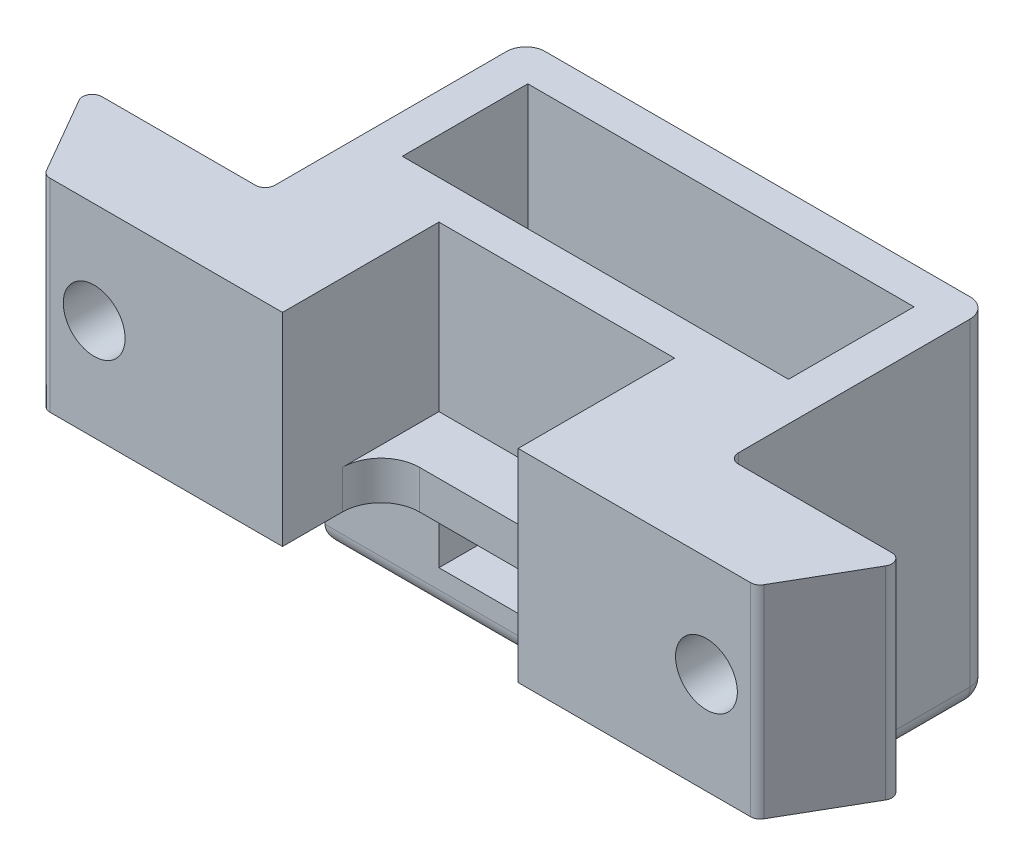
SolidWorks part; units mm, degrees
ref_plane "Front Plane" through (0, 0, 0) normal (0, 0, 1) x (1, 0, 0)
ref_plane "Top Plane" through (0, 0, 0) normal (0, 1, 0) x (1, 0, 0)
ref_plane "Right Plane" through (0, 0, 0) normal (1, 0, 0) x (0, 0, -1)
sketch "Sketch1" plane through (0, 0, 0) normal (0, 1, 0) x (1, 0, 0)
  line L0 (0, 0) -> (0, 8.1)
  line L1 (0, 8.1) -> (12.2, 8.1)
  line L2 (12.2, 8.1) -> (12.2, 0)
  line L3 (-15.5, 0) -> (-15.5, 4.5)
  line L4 (16.1, 10.1) -> (-3.9, 10.1)
  line L5 (-3.9, 10.1) -> (-3.9, 16.6)
  line L6 (-3.9, 16.6) -> (16.1, 16.6)
  line L7 (16.1, 16.6) -> (16.1, 10.1)
  line L9 (-15, 5) -> (-6.4, 5)
  line L10 (27.7, 0) -> (27.7, 4.5)
  line L11 (27.2, 5) -> (18.6, 5)
  line L12 (0, 0) -> (-15.5, 0)
  line L13 (12.2, 0) -> (27.7, 0)
  line L14 (17.1, 18.5) -> (-4.9, 18.5)
  line L15 (18.1, 5.5) -> (18.1, 17.5)
  line L16 (-5.9, 5.5) -> (-5.9, 17.5)
  arc A0 (27.7, 4.5) -> (27.2, 5) centre (27.2, 4.5) ccw
  arc A1 (-15.5, 4.5) -> (-15, 5) centre (-15, 4.5) cw
  arc A2 (18.6, 5) -> (18.1, 5.5) centre (18.6, 5.5) cw
  arc A3 (-5.9, 5.5) -> (-6.4, 5) centre (-6.4, 5.5) cw
  arc A4 (18.1, 17.5) -> (17.1, 18.5) centre (17.1, 17.5) ccw
  arc A5 (-4.9, 18.5) -> (-5.9, 17.5) centre (-4.9, 17.5) ccw
  dimension "D1" = 0.5
  dimension "D2" = 0.5
  dimension "D3" = 1
extrude "Boss-Extrude1" add sketch "Sketch1" along normal blind 10.5
sketch "Sketch5" plane through (0, 0, 0) normal (0, -1, 0) x (1, 0, 0)
  line L0 (0, -8.1) -> (-5.9, -8.1)
  line L1 (17.1, -18.5) -> (-4.9, -18.5)
  line L2 (-5.9, -8.1) -> (-5.9, -17.5)
  line L4 (0, -8.1) -> (0, -10.1)
  line L7 (12.2, -8.1) -> (18.1, -8.1)
  line L8 (-3.9, -10.1) -> (16.1, -10.1) construction
  line L9 (0, -10.1) -> (-3.9, -10.1)
  line L10 (-3.9, -10.1) -> (-3.9, -16.6)
  line L11 (-3.9, -16.6) -> (16.1, -16.6)
  line L12 (16.1, -16.6) -> (16.1, -10.1)
  line L13 (16.1, -10.1) -> (12.2, -10.1)
  line L14 (12.2, -10.1) -> (12.2, -8.1)
  line L15 (18.1, -8.1) -> (18.1, -17.5)
  arc A0 (17.1, -18.5) -> (18.1, -17.5) centre (17.1, -17.5) ccw
  arc A1 (-5.9, -17.5) -> (-4.9, -18.5) centre (-4.9, -17.5) ccw
  dimension "D1" = 1
extrude "Boss-Extrude2" add sketch "Sketch5" along normal blind 5
sketch "Sketch6" plane through (0, -5, 0) normal (0, -1, 0) x (1, 0, 0)
  line L0 (-5.9, -8.1) -> (18.1, -8.1)
  line L1 (17.1, -18.5) -> (-4.9, -18.5)
  line L4 (-5.9, -8.1) -> (-5.9, -17.5)
  line L6 (18.1, -8.1) -> (18.1, -17.5)
  arc A0 (17.1, -18.5) -> (18.1, -17.5) centre (17.1, -17.5) ccw
  arc A1 (-4.9, -18.5) -> (-5.9, -17.5) centre (-4.9, -17.5) cw
  dimension "D1" = 1
extrude "Boss-Extrude3" add sketch "Sketch6" along normal blind 2
sketch "Sketch7" plane through (0, 0, -8.1) normal (0, 0, 1) x (1, 0, 0)
  line L0 (0, 0) -> (0, 2)
  line L1 (0, 10.5) -> (0, 0) construction
  line L2 (0, 2) -> (12.2, 2)
  line L3 (12.2, 10.5) -> (12.2, 0) construction
  line L4 (12.2, 2) -> (12.2, 0)
  line L5 (12.2, 0) -> (0, 0)
extrude "Boss-Extrude5" add sketch "Sketch7" along normal blind 3
fillet "Fillet2" radius 2 2 edges at (12.2, 1, -5.1) (0, 1, -5.1)
sketch "Sketch8" plane through (0, 0, -5) normal (0, 0, -1) x (-1, 0, 0)
  circle A0 centre (-21.95, 5.25) radius 1.6
  circle A1 centre (9.75, 5.25) radius 1.6
extrude "Cut-Extrude2" cut sketch "Sketch8" against normal up to next
sketch "Sketch9" plane through (0, 0, 0) normal (0, -1, 0) x (1, 0, 0)
  line L0 (24.5277, 0) -> (27.3922, -4.9616)
  line L1 (27.7, 0) -> (27.7, -4.5)
  line L2 (-12.3277, 0) -> (-15.5, 0)
  line L4 (24.5277, 0) -> (27.7, 0)
  line L6 (-15.5, -4.5) -> (-15.5, 0)
  line L11 (-12.3277, 0) -> (-15.1922, -4.9616)
  arc A0 (27.7, -4.5) -> (27.3922, -4.9616) centre (27.2, -4.5) cw
  arc A1 (-15.5, -4.5) -> (-15.1922, -4.9616) centre (-15, -4.5) ccw
  dimension "D1" = 60
extrude "Cut-Extrude3" cut sketch "Sketch9" against normal up to next
fillet "Fillet8" radius 0.5 4 edges at (27.3922, 5.25, -4.9616) (24.5277, 5.25, 0) (-15.1922, 5.25, -4.9616) (-12.3277, 5.25, 0)
fillet "Fillet9" radius 1 6 edges at (-5.9, -7, -12.8) (18.1, -7, -12.8) (6.1, -7, -8.1) (-5.6071, -7, -18.2071) (6.1, -7, -18.5) (17.8071, -7, -18.2071)
sketch "Sketch10" plane through (0, 0, -18.5) normal (0, 0, -1) x (-1, 0, 0)
  circle A0 centre (-11.25, 2.75) radius 1.25
  circle A1 centre (-1.9, 2.75) radius 1.25
extrude "Cut-Extrude4" cut sketch "Sketch10" against normal up to next
